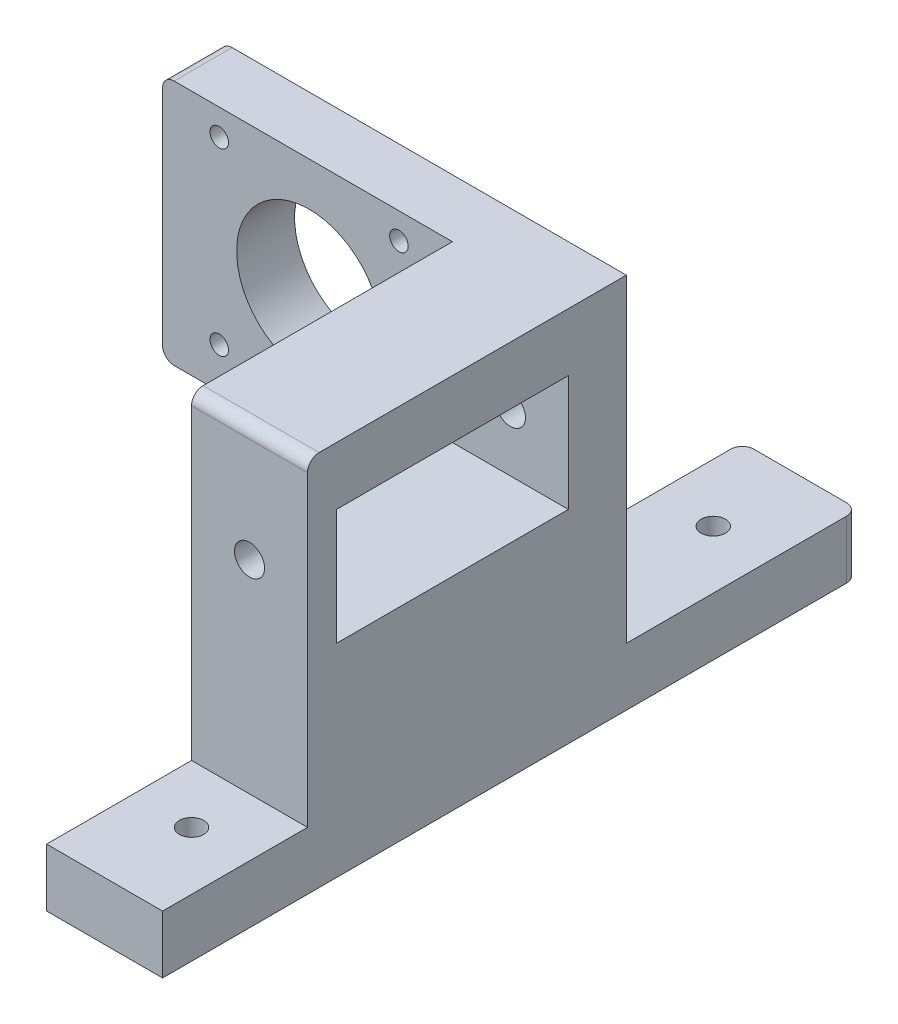
SolidWorks part; units mm, degrees
ref_plane "Front Plane" through (0, 0, 0) normal (0, 0, 1) x (1, 0, 0)
ref_plane "Top Plane" through (0, 0, 0) normal (0, 1, 0) x (1, 0, 0)
ref_plane "Right Plane" through (0, 0, 0) normal (1, 0, 0) x (0, 0, -1)
sketch "Sketch4" plane through (0, 0, 0) normal (0, 1, 0) x (1, 0, 0)
  line L1 (0, 0) -> (20, 0)
  line L2 (0, 0) -> (0, 120)
  line L3 (0, 120) -> (20, 120)
  line L4 (20, 0) -> (20, 120)
  dimension "D1" = 120
  dimension "D2" = 20
extrude "Boss-Extrude4" add sketch "Sketch4" along normal blind 10
sketch "Sketch5" plane through (0, 10, 0) normal (0, 1, 0) x (1, 0, 0)
  line L0 (10, 0) -> (10, 15) construction
  line L1 (0, 0) -> (20, 0) construction
  line L2 (10, 120) -> (10, 105) construction
  line L3 (20, 120) -> (0, 120) construction
  circle A0 centre (10, 105) radius 2.1
  circle A1 centre (10, 15) radius 2.1
  dimension "D3" = 4.2
  dimension "D4" = 4.2
  dimension "D1" = 15
  dimension "D2" = 15
extrude "Cut-Extrude1" cut sketch "Sketch5" against normal blind 10
sketch "Sketch8" plane through (0, 10, 0) normal (0, 1, 0) x (1, 0, 0)
  line L0 (20, 0) -> (20, 120) construction
  line L1 (20, 25) -> (0, 25)
  line L2 (20, 25) -> (20, 80)
  line L3 (20, 80) -> (0, 80)
  line L4 (0, 25) -> (0, 80)
  line L5 (0, 0) -> (20, 0) construction
  dimension "D1" = 55
  dimension "D2" = 20
  dimension "D3" = 25
extrude "Boss-Extrude6" add sketch "Sketch8" along normal blind 55
sketch "Sketch9" plane through (0, 0, 0) normal (-1, 0, 0) x (0, 0, 1)
  line L0 (-80, 65) -> (-80, 10) construction
  line L5 (-70, 55) -> (-30, 55)
  line L6 (-70, 55) -> (-70, 35)
  line L7 (-70, 35) -> (-30, 35)
  line L8 (-30, 55) -> (-30, 35)
  line L9 (-80, 65) -> (-25, 65) construction
  dimension "D1" = 20
  dimension "D2" = 40
  dimension "D3" = 10
  dimension "D4" = 10
extrude "Cut-Extrude2" cut sketch "Sketch9" against normal blind 20
sketch "Sketch11" plane through (0, 0, -70) normal (0, 0, 1) x (1, 0, 0)
  line L0 (0, 45) -> (20, 45)
  line L1 (0, 55) -> (0, 35) construction
  line L2 (20, 55) -> (20, 35) construction
  circle A0 centre (10, 45) radius 2.6
  dimension "D1" = 5.2
extrude "Cut-Extrude3" cut sketch "Sketch11" against normal mid plane 100 contours A0
sketch "Sketch12" plane through (0, 0, 0) normal (-1, 0, 0) x (0, 0, 1)
  line L1 (-80, 65) -> (-70, 65)
  line L2 (-80, 65) -> (-80, 10)
  line L3 (-80, 10) -> (-70, 10)
  line L4 (-70, 65) -> (-70, 10)
  dimension "D1" = 55
  dimension "D2" = 10
extrude "Boss-Extrude7" add sketch "Sketch12" along normal blind 50
sketch "Sketch15" plane through (0, 0, -70) normal (0, 0, 1) x (1, 0, 0)
  line L0 (0, 65) -> (20, 65) construction
  line L1 (-40.2253, 60.5002) -> (-9.2253, 60.5002)
  line L2 (-40.2253, 60.5002) -> (-40.2253, 29.5002)
  line L3 (-40.2253, 29.5002) -> (-9.2253, 29.5002)
  line L4 (-9.2253, 60.5002) -> (-9.2253, 29.5002)
  line L5 (-40.2253, 60.5002) -> (-9.2253, 29.5002) construction
  line L6 (-40.2253, 29.5002) -> (-9.2253, 60.5002) construction
  line L7 (-50, 10) -> (-50, 65) construction
  line L8 (-50, 65) -> (0, 65) construction
  circle A0 centre (-24.7253, 45.0002) radius 12.5
  circle A1 centre (-9.2253, 60.5002) radius 1.6
  circle A2 centre (-9.2253, 29.5002) radius 1.6
  circle A3 centre (-40.2253, 29.5002) radius 1.6
  circle A4 centre (-40.2253, 60.5002) radius 1.6
  point P19 (-24.7253, 45.0002)
  dimension "D1" = 25
  dimension "D6" = 3.2
  dimension "D2" = 31
  dimension "D3" = 19.9998
  dimension "D4" = 9.7747
  dimension "D5" = 4.4998
extrude "Cut-Extrude4" cut sketch "Sketch15" against normal up to surface (10 mm away) contours A0 | L4 A1 L1 | L1 A1 L4 | L3 A2 L4 | L4 A2 L3 | L2 A3 L3 | L3 A3 L2 | L2 A4 L1 | L1 A4 L2 region at (-40.4516, 60.7266, -70) region at (-39.5462, 59.8212, -70) region at (-8.9989, 60.7266, -70) region at (-9.9043, 59.8212, -70) region at (-39.5462, 30.1793, -70) region at (-40.4516, 29.2739, -70) region at (-8.9989, 29.2739, -70) region at (-9.9043, 30.1793, -70) region at (-24.7253, 45.0002, -70) up to face at (12.6, 45, -80)
sketch "Sketch17" plane through (0, 0, -70) normal (0, 0, 1) x (1, 0, 0)
  line L1 (-50, 10) -> (0, 10)
  line L2 (-50, 10) -> (-50, 22.5)
  line L3 (-50, 22.5) -> (0, 22.5)
  line L4 (0, 10) -> (0, 22.5)
  line L5 (0, 10) -> (0, 35) construction
  dimension "D1" = 12.5
  dimension "D2" = 50
extrude "Cut-Extrude6" cut sketch "Sketch17" against normal up to surface (10 mm away) contours L2 L1 L4 L3 up to face at (-38.6253, 60.5002, -80)
chamfer "Chamfer1" distance 12.5 angle 45 1 edges at (0, 22.5, -75)
fillet "Fillet1" radius 2 5 edges at (20, 5, -120) (0, 5, -120) (10, 65, -25) (-50, 65, -75) (-50, 22.5, -75)
